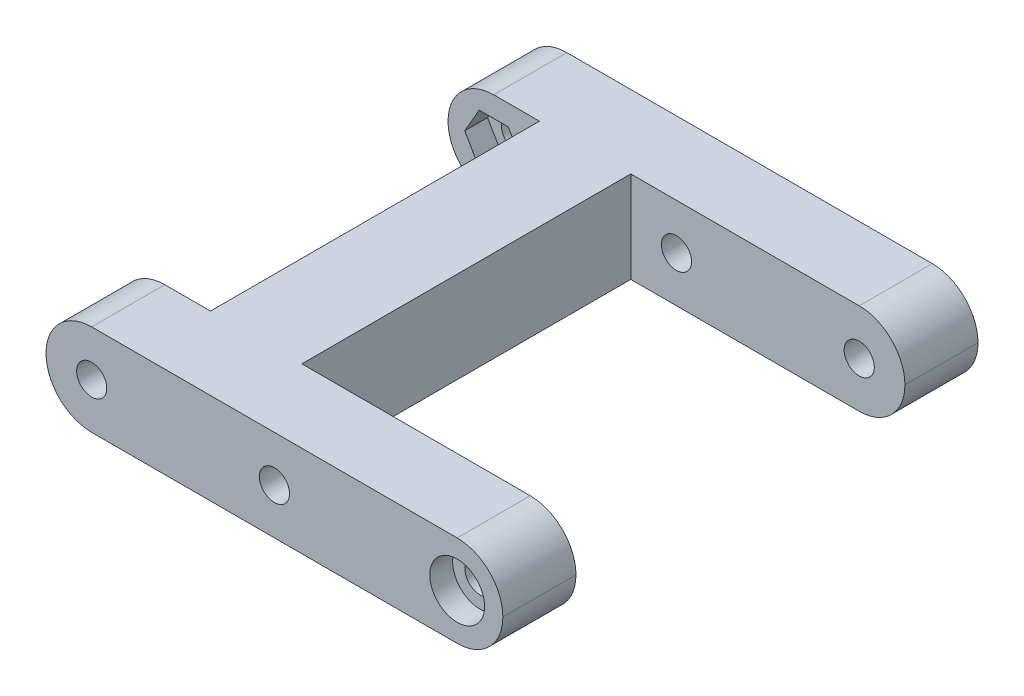
SolidWorks part; units mm, degrees
ref_plane "Přední rovina" through (0, 0, 0) normal (0, 0, 1) x (1, 0, 0)
ref_plane "Horní rovina" through (0, 0, 0) normal (0, 1, 0) x (1, 0, 0)
ref_plane "Pravá rovina" through (0, 0, 0) normal (1, 0, 0) x (0, 0, -1)
sketch "Skica1" plane through (0, 0, 0) normal (0, 0, 1) x (1, 0, 0)
  line L1 (0, 0) -> (50, 0)
  line L2 (0, 0) -> (0, 10)
  line L3 (0, 10) -> (50, 10)
  line L4 (50, 0) -> (50, 10)
  dimension "D1" = 50
  dimension "D2" = 10
extrude "Přidat vysunutím1" add sketch "Skica1" along normal blind 8
sketch "Skica2" plane through (0, 0, 8) normal (0, 0, 1) x (1, 0, 0)
  line L0 (0, 0) -> (50, 0) construction
  line L1 (0, 10) -> (0, 0) construction
  line L2 (50, 0) -> (50, 10) construction
  circle A0 centre (5, 5) radius 1.65
  circle A1 centre (45, 5) radius 1.65
  dimension "D1" = 3.3
  dimension "D2" = 3.3
  dimension "D3" = 5
  dimension "D4" = 5
  dimension "D5" = 5
  dimension "D6" = 5
extrude "Odebrat vysunutím1" cut sketch "Skica2" against normal through all
fillet "Zaoblit2" radius 5 4 edges at (50, 0, 4) (50, 10, 4) (0, 0, 4) (0, 10, 4)
sketch "Skica4" plane through (0, 0, 8) normal (0, 0, 1) x (1, 0, 0)
  line L0 (45, 10) -> (5, 10) construction
  circle A0 centre (25, 5) radius 1.65
  dimension "D1" = 3.3
  dimension "D2" = 5
  dimension "D3" = 25
extrude "Odebrat vysunutím2" cut sketch "Skica4" against normal blind 10
sketch "Skica5" plane through (0, 0, 0) normal (0, 0, -1) x (-1, 0, 0)
  line L0 (-45, 10) -> (-5, 10) construction
  line L1 (-1.8246, 5) -> (-3.4123, 7.75)
  line L2 (-3.4123, 7.75) -> (-6.5877, 7.75)
  line L3 (-6.5877, 7.75) -> (-8.1754, 5)
  line L4 (-8.1754, 5) -> (-6.5877, 2.25)
  line L5 (-6.5877, 2.25) -> (-3.4123, 2.25)
  line L6 (-3.4123, 2.25) -> (-1.8246, 5)
  circle A0 centre (-5, 5) radius 2.75 construction
  dimension "D1" = 5.5
  dimension "D2" = 60
extrude "Odebrat vysunutím3" cut sketch "Skica5" against normal blind 2.5
sketch "Skica6" plane through (0, 0, 8) normal (0, 0, 1) x (1, 0, 0)
  circle A0 centre (45, 5) radius 3
  dimension "D1" = 6
extrude "Odebrat vysunutím4" cut sketch "Skica6" against normal blind 2.5
sketch "Skica7" plane through (0, 0, 0) normal (0, 0, -1) x (-1, 0, 0)
  line L0 (-45, 10) -> (-5, 10) construction
  line L1 (-10, 10) -> (-20, 10)
  line L2 (-10, 10) -> (-10, 0)
  line L3 (-10, 0) -> (-20, 0)
  line L4 (-20, 10) -> (-20, 0)
  line L5 (-5, 0) -> (-45, 0) construction
  dimension "D1" = 10
  dimension "D2" = 10
extrude "Přidat vysunutím2" add sketch "Skica7" along normal blind 36
sketch "Skica8" plane through (0, 0, -36) normal (0, 0, -1) x (-1, 0, 0)
  line L1 (0, 0) -> (-50, 0)
  line L2 (0, 0) -> (0, 10)
  line L3 (0, 10) -> (-50, 10)
  line L4 (-50, 0) -> (-50, 10)
  dimension "D1" = 10
  dimension "D2" = 50
extrude "Přidat vysunutím3" add sketch "Skica8" along normal blind 8
fillet "Zaoblit3" radius 5 4 edges at (0, 0, -40) (0, 10, -40) (50, 0, -40) (50, 10, -40)
sketch "Skica9" plane through (0, 0, -44) normal (0, 0, -1) x (-1, 0, 0)
  line L0 (-5, 10) -> (-45, 10) construction
  circle A0 centre (-45, 5) radius 1.65
  circle A1 centre (-5, 5) radius 1.65
  dimension "D1" = 3.3
  dimension "D2" = 3.3
  dimension "D3" = 5
  dimension "D4" = 5
  dimension "D5" = 5
  dimension "D6" = 5
extrude "Odebrat vysunutím5" cut sketch "Skica9" against normal blind 8
sketch "Skica10" plane through (0, 0, -44) normal (0, 0, -1) x (-1, 0, 0)
  circle A0 centre (-45, 5) radius 2.75
  dimension "D1" = 5.5
extrude "Odebrat vysunutím6" cut sketch "Skica10" against normal blind 2.5
sketch "Skica11" plane through (0, 0, -36) normal (0, 0, 1) x (1, 0, 0)
  line L1 (1.8246, 5) -> (3.4123, 2.25)
  line L2 (3.4123, 2.25) -> (6.5877, 2.25)
  line L3 (6.5877, 2.25) -> (8.1754, 5)
  line L4 (8.1754, 5) -> (6.5877, 7.75)
  line L5 (6.5877, 7.75) -> (3.4123, 7.75)
  line L6 (3.4123, 7.75) -> (1.8246, 5)
  line L7 (20, 10) -> (45, 10) construction
  circle A0 centre (5, 5) radius 2.75 construction
  dimension "D1" = 5.5
  dimension "D2" = 60
extrude "Odebrat vysunutím7" cut sketch "Skica11" against normal blind 2.5
sketch "Skica12" plane through (0, 0, -44) normal (0, 0, -1) x (-1, 0, 0)
  line L0 (-45, 0) -> (-5, 0) construction
  circle A0 centre (-25, 5) radius 1.65
  dimension "D3" = 3.3
  dimension "D1" = 25
  dimension "D2" = 5
extrude "Odebrat vysunutím8" cut sketch "Skica12" against normal blind 36
